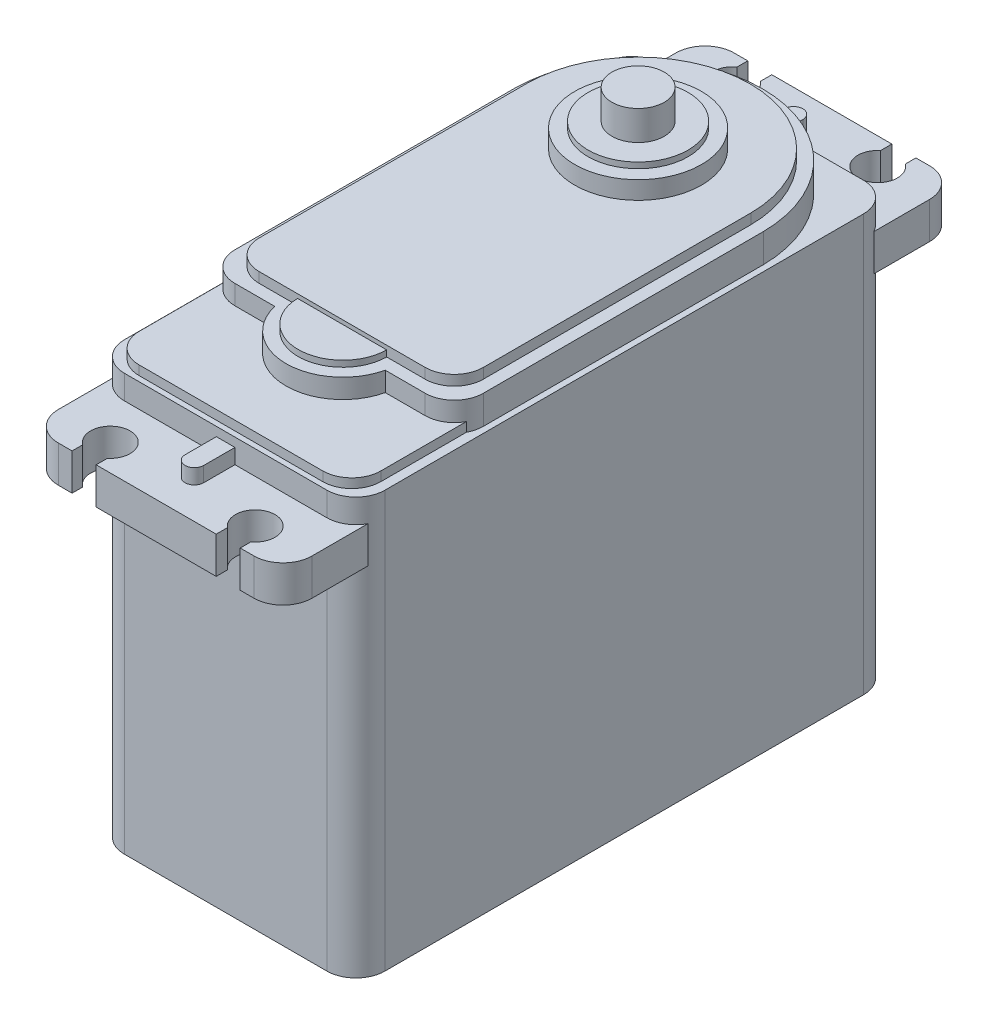
SolidWorks part; units mm, degrees
ref_plane "Front Plane" through (0, 0, 0) normal (0, 0, 1) x (1, 0, 0)
ref_plane "Top Plane" through (0, 0, 0) normal (0, 1, 0) x (1, 0, 0)
ref_plane "Right Plane" through (0, 0, 0) normal (1, 0, 0) x (0, 0, -1)
ref_plane "Plane1" through (28.4734, 0, 0) normal (1, 0, 0) x (0, 0, -1)
sketch "Sketch1" plane through (28.4734, 0, 0) normal (1, 0, 0) x (0, 0, -1)
  line L0 (-20.6785, -27.9934) -> (37.9701, -27.9934)
  line L1 (37.9701, -27.9934) -> (37.9701, 17.5234)
  line L2 (37.9701, 17.5234) -> (-20.6785, 17.5234)
  line L3 (-20.6785, 17.5234) -> (-20.6785, -27.9934)
extrude "Boss-Extrude1" add sketch "Sketch1" against normal blind 28.4734
sketch "Sketch2" plane through (0, 17.5234, 0) normal (0, 1, 0) x (-1, 0, 0)
  line L0 (-27.4447, 20.1007) -> (-1.0287, 20.1007)
  line L1 (-1.0287, 20.1007) -> (-1.0287, 7.5832)
  line L2 (-0.6604, 6.0989) -> (-0.6604, -24.4974)
  line L3 (-10.3179, -37.3922) -> (-18.1555, -37.3922)
  line L4 (-27.813, -24.4974) -> (-27.813, 6.0989)
  line L5 (-27.4447, 7.5832) -> (-27.4447, 20.1007)
  arc A0 (-1.0287, 7.5832) -> (-0.6604, 6.0989) centre (-3.8354, 6.0989) cw
  arc A1 (-0.6604, -24.4974) -> (-10.3179, -37.3922) centre (-14.2367, -24.3934) cw
  arc A2 (-18.1555, -37.3922) -> (-27.813, -24.4974) centre (-14.2367, -24.3934) cw
  arc A3 (-27.813, 6.0989) -> (-27.4447, 7.5832) centre (-24.638, 6.0989) cw
extrude "Boss-Extrude2" add sketch "Sketch2" along normal blind 1.016
sketch "Sketch3" plane through (0, 18.5394, 0) normal (0, 1, 0) x (-1, 0, 0)
  line L0 (-0.6604, 6.0989) -> (-0.6604, -24.4974)
  line L1 (-27.813, -24.4974) -> (-27.813, 6.0989)
  line L2 (-24.638, 9.2739) -> (-3.8354, 9.2739)
  arc A0 (-3.8354, 9.2739) -> (-0.6604, 6.0989) centre (-3.8354, 6.0989) cw
  arc A1 (-0.6604, -24.4974) -> (-27.813, -24.4974) centre (-14.2367, -24.3934) cw
  arc A2 (-27.813, 6.0989) -> (-24.638, 9.2739) centre (-24.638, 6.0989) cw
extrude "Boss-Extrude3" add sketch "Sketch3" along normal blind 2.1209
sketch "Sketch4" plane through (0, 0, 20.6785) normal (0, 0, 1) x (1, 0, 0)
  line L0 (0.3746, 10.9067) -> (0.3746, 14.9072)
  line L1 (0.3746, 14.9072) -> (28.0988, 14.9072)
  line L2 (28.0988, 14.9072) -> (28.0988, 10.9067)
  line L3 (28.0988, 10.9067) -> (0.3746, 10.9067)
extrude "Boss-Extrude4" add sketch "Sketch4" along normal blind 7.5946
sketch "Sketch5" plane through (0, 10.9067, 0) normal (0, -1, 0) x (1, 0, 0)
  line L0 (7.6772, 28.2731) -> (5.0483, 28.2731)
  line L1 (5.0483, 28.2731) -> (5.0483, 27.1108)
  line L2 (7.6772, 27.0425) -> (7.6772, 28.2731)
  arc A0 (5.0483, 27.1108) -> (7.6772, 27.0425) centre (6.3183, 25.3648) cw
extrude "Cut-Extrude1" cut sketch "Sketch5" against normal through all
sketch "Sketch6" plane through (0, 10.9067, 0) normal (0, -1, 0) x (1, 0, 0)
  line L0 (23.4252, 28.2731) -> (20.7963, 28.2731)
  line L1 (20.7963, 28.2731) -> (20.7962, 27.0425)
  line L2 (23.4251, 27.1108) -> (23.4252, 28.2731)
  arc A0 (20.7962, 27.0425) -> (23.4251, 27.1108) centre (22.1551, 25.3648) cw
extrude "Cut-Extrude2" cut sketch "Sketch6" against normal through all
sketch "Sketch7" plane through (0, 18.5394, 0) normal (0, 1, 0) x (-1, 0, 0)
  line L0 (-8.1986, 9.2739) -> (-20.2748, 9.2739)
  arc A0 (-20.2748, 9.2739) -> (-8.1986, 9.2739) centre (-14.2367, 7.8769) cw
extrude "Boss-Extrude5" add sketch "Sketch7" along normal blind 2.1209
sketch "Sketch8" plane through (0, 14.9072, 0) normal (0, 1, 0) x (-1, 0, 0)
  line L0 (-13.2207, 24.0948) -> (-13.2207, 20.6785)
  line L1 (-13.2207, 20.6785) -> (-15.2527, 20.6785)
  line L2 (-15.2527, 20.6785) -> (-15.2527, 24.0948)
  arc A0 (-15.2527, 24.0948) -> (-13.2207, 24.0948) centre (-14.2367, 24.0948) cw
extrude "Boss-Extrude6" add sketch "Sketch8" along normal blind 1.6383
sketch "Sketch9" plane through (0, 20.6603, 0) normal (0, 1, 0) x (-1, 0, 0)
  line L0 (-26.4859, -24.4922) -> (-26.4859, 7.9468)
  line L1 (-26.4859, 7.9468) -> (-1.9876, 7.9468)
  line L2 (-1.9876, 7.9468) -> (-1.9876, -24.4922)
  arc A0 (-1.9876, -24.4922) -> (-26.4859, -24.4922) centre (-14.2367, -24.3934) cw
extrude "Boss-Extrude7" add sketch "Sketch9" along normal blind 1.1176
sketch "Sketch10" plane through (0, 20.6603, 0) normal (0, 1, 0) x (-1, 0, 0)
  line L0 (-9.3668, 7.9468) -> (-19.1066, 7.9468)
  arc A0 (-19.1066, 7.9468) -> (-9.3668, 7.9468) centre (-14.2367, 7.8769) cw
extrude "Boss-Extrude8" add sketch "Sketch10" along normal blind 0.6731
sketch "Sketch11" plane through (0, 0, -37.9701) normal (0, 0, -1) x (-1, 0, 0)
  line L0 (-10.5156, -24.4247) -> (-17.9578, -24.4247)
  line L1 (-17.9578, -24.4247) -> (-17.9578, -20.9449)
  line L2 (-17.9578, -20.9449) -> (-10.5156, -20.9449)
  line L3 (-10.5156, -20.9449) -> (-10.5156, -24.4247)
extrude "Boss-Extrude9" add sketch "Sketch11" along normal blind 6.1214 draft 10
sketch "Sketch12" plane through (0, 0, -37.9701) normal (0, 0, -1) x (-1, 0, 0)
  line L0 (-28.0988, 10.9067) -> (-28.0988, 14.9072)
  line L1 (-28.0988, 14.9072) -> (-0.3746, 14.9072)
  line L2 (-0.3746, 14.9072) -> (-0.3746, 10.9067)
  line L3 (-0.3746, 10.9067) -> (-28.0988, 10.9067)
extrude "Boss-Extrude10" add sketch "Sketch12" along normal blind 7.5946
ref_plane "Plane2" through (0, 0, 25.3648) normal (0, 0, 1) x (1, 0, 0)
sketch "Sketch13" plane through (0, 0, 25.3648) normal (0, 0, 1) x (1, 0, 0)
  line L0 (8.4773, 14.9072) -> (6.3183, 14.9072)
  line L1 (6.3183, 14.9072) -> (6.3183, 10.9067)
  line L2 (6.3183, 10.9067) -> (8.4773, 10.9067)
  line L3 (8.4773, 10.9067) -> (8.4773, 14.9072)
  line L4 (6.3183, 14.9072) -> (6.3183, 10.9067) construction
revolve "Cut-Revolve1" cut sketch "Sketch13" angle 360 about L4 reverse direction yes
sketch "Sketch14" plane through (0, 0, 25.3648) normal (0, 0, 1) x (1, 0, 0)
  line L0 (24.3142, 14.9072) -> (22.1551, 14.9072)
  line L1 (22.1551, 14.9072) -> (22.1551, 10.9067)
  line L2 (22.1551, 10.9067) -> (24.3141, 10.9067)
  line L3 (24.3141, 10.9067) -> (24.3142, 14.9072)
  line L4 (22.1551, 14.9072) -> (22.1551, 10.9067) construction
revolve "Cut-Revolve2" cut sketch "Sketch14" angle 360 about L4 reverse direction yes
ref_plane "Plane3" through (0, 0, -24.3934) normal (0, 0, 1) x (1, 0, 0)
sketch "Sketch15" plane through (0, 0, -24.3934) normal (0, 0, 1) x (1, 0, 0)
  line L0 (17.0942, 27.5945) -> (14.2367, 27.5945)
  line L1 (14.2367, 27.5945) -> (14.2367, 21.7779)
  line L2 (14.2367, 21.7779) -> (21.1645, 21.7779)
  line L3 (21.1645, 21.7779) -> (21.1645, 23.7337)
  line L4 (21.1645, 23.7337) -> (19.6977, 23.7337)
  line L5 (19.6977, 23.7337) -> (19.6977, 24.3687)
  line L6 (19.6977, 24.3687) -> (17.0942, 24.3687)
  line L7 (17.0942, 24.3687) -> (17.0942, 27.5945)
  line L8 (14.2367, 27.5945) -> (14.2367, 21.7779) construction
revolve "Revolve1" add sketch "Sketch15" angle 360 about L8 reverse direction yes
ref_plane "Plane4" through (14.2367, 0, 0) normal (1, 0, 0) x (0, 0, -1)
fillet "Fillet1" radius 3.175 1 edges at (27.4447, 18.0314, 20.1007) tangent propagation no
fillet "Fillet2" radius 3.175 1 edges at (1.0287, 18.0314, 20.1007) tangent propagation no
fillet "Fillet3" radius 3.175 1 edges at (0, -5.235, -37.9701) tangent propagation no
fillet "Fillet4" radius 3.175 1 edges at (0.3746, 12.9069, 28.2731) tangent propagation no
fillet "Fillet5" radius 3.175 1 edges at (28.4734, -5.235, -37.9701) tangent propagation no
fillet "Fillet6" radius 3.175 1 edges at (1.9876, 21.2191, 7.9468) tangent propagation no
fillet "Fillet7" radius 3.175 1 edges at (28.4734, -5.235, 20.6785) tangent propagation no
fillet "Fillet8" radius 3.175 1 edges at (0, -5.235, 20.6785) tangent propagation no
fillet "Fillet9" radius 3.175 1 edges at (0.3746, 12.9069, -45.5647) tangent propagation no
fillet "Fillet10" radius 3.175 1 edges at (28.0988, 12.9069, -45.5647) tangent propagation no
fillet "Fillet11" radius 3.175 1 edges at (26.4859, 21.2191, 7.9468) tangent propagation no
fillet "Fillet12" radius 3.175 1 edges at (28.0988, 12.9069, 28.2731) tangent propagation no
sketch "Sketch17" plane through (28.4734, 0, 0) normal (1, 0, 0) x (0, 0, -1)
  line L0 (8.6458, -27.9934) -> (8.6458, 14.9072) construction
  line L3 (-28.2731, 14.9072) -> (45.5647, 14.9072)
ref_plane "Plane5" through (0, 0, -8.6458) normal (0, 0, 1) x (1, 0, 0)
mirror "Mirror1" about plane through (0, 0, -8.6458) normal (0, 0, 1) of "Boss-Extrude6", "Cut-Revolve2", "Cut-Revolve1", "Cut-Extrude2", "Cut-Extrude1"
